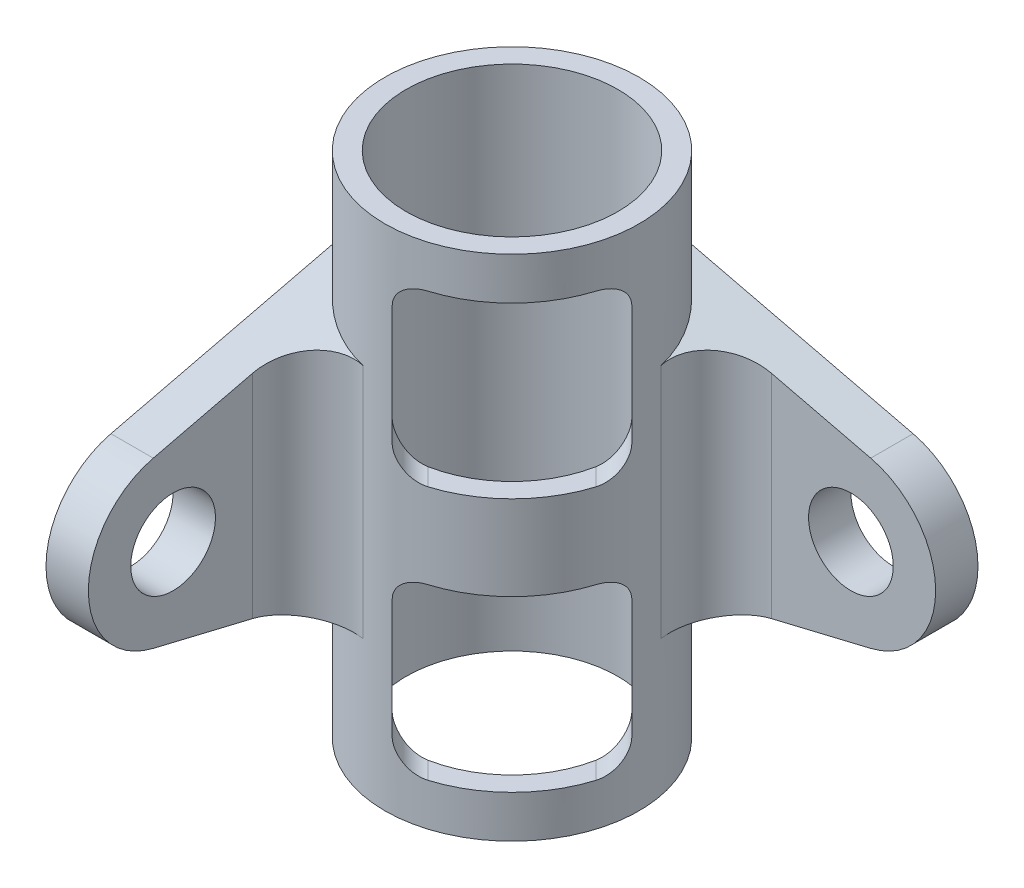
SolidWorks part; units mm, degrees
ref_plane "前基準面" through (0, 0, 0) normal (0, 0, 1) x (1, 0, 0)
ref_plane "上基準面" through (0, 0, 0) normal (0, 1, 0) x (1, 0, 0)
ref_plane "右基準面" through (0, 0, 0) normal (1, 0, 0) x (0, 0, -1)
sketch "草圖1" plane through (0, 0, 0) normal (0, 1, 0) x (1, 0, 0)
  circle A0 centre (0, 0) radius 12.5
  circle A1 centre (0, 0) radius 15
  dimension "D1" = 25
  dimension "D2" = 30
extrude "填料-伸長3" add sketch "草圖1" along normal mid plane 60 contours A1
ref_plane "平面2" through (-15, 0, 0) normal (-1, 0, 0) x (0, 0, 1)
ref_plane "平面3" through (0, 0, -15) normal (0, 0, -1) x (-1, 0, 0)
sketch "草圖4" plane through (-15, 0, 0) normal (-1, 0, 0) x (0, 0, 1)
  line L0 (0, -17.5) -> (0, 17.5)
  line L1 (32.3383, -9.7228) -> (0, -17.5)
  line L2 (32.3383, 9.7228) -> (0, 17.5)
  circle A0 centre (30, 0) radius 5
  arc A1 (32.3383, -9.7228) -> (32.3383, 9.7228) centre (30, 0) ccw
  point P4 (0, 0)
  dimension "D2" = 30
  dimension "D3" = 10
  dimension "D4" = 10
  dimension "D1" = 35
extrude "填料-伸長4" add sketch "草圖4" against normal blind 5
sketch "草圖5" plane through (0, 0, -15) normal (0, 0, -1) x (-1, 0, 0)
  line L0 (0, -17.5) -> (0, 17.5)
  line L1 (-32.3383, -9.7228) -> (0, -17.5)
  line L2 (-32.3383, 9.7228) -> (0, 17.5)
  circle A0 centre (-30, 0) radius 5
  arc A1 (-32.3383, -9.7228) -> (-32.3383, 9.7228) centre (-30, 0) cw
  point P4 (0, 0)
  point P9 (0, 0)
  point P10 (0, 0)
  dimension "D2" = 30
  dimension "D3" = 10
  dimension "D4" = 10
  dimension "D1" = 35
extrude "填料-伸長5" add sketch "草圖5" against normal blind 5
fillet "圓角1" radius 6 2 edges at (11.1803, 0, -10) (-10, 0, 11.1803)
ref_axis "基準軸1" through (0, 33, 0) along (0, -1, 0)
ref_plane "平面4" through (0, 0, 0) normal (-0.7071, 0, 0.7071) x (0, -1, 0)
sketch "草圖6" plane through (0, 0, 0) normal (-0.7071, 0, 0.7071) x (0, -1, 0)
  line L0 (30, 15) -> (-30, 15) construction
  line L1 (30, 15) -> (-30, 15)
ref_plane "平面5" through (10.6066, 0, 10.6066) normal (0.7071, 0, 0.7071) x (0.7071, 0, -0.7071)
extrude "除料-伸長4" cut sketch "草圖1<3>" against normal through all both and the other way through all contours A0
sketch "草圖1<3>" plane through (0, 0, 0) normal (0, 1, 0) x (1, 0, 0) same geometry as "草圖1"
sketch "草圖7" plane through (10.6066, 0, 10.6066) normal (0.7071, 0, 0.7071) x (0.7071, 0, -0.7071)
  line L0 (-15.6821, 0) -> (15.9807, 0) construction
  line L1 (0, -30) -> (0, 30) construction
  line L2 (-7, 25) -> (7, 25)
  line L3 (-10, 22) -> (-10, 8)
  line L4 (-7, 5) -> (7, 5)
  line L5 (10, 22) -> (10, 8)
  line L6 (-10, 25) -> (10, 5) construction
  line L7 (-10, 5) -> (10, 25) construction
  line L9 (15, 30) -> (-15, 30) construction
  line L10 (-7, -5) -> (7, -5)
  line L11 (10, -22) -> (10, -8)
  line L12 (-7, -25) -> (7, -25)
  line L13 (-10, -22) -> (-10, -8)
  arc A0 (-10, 22) -> (-7, 25) centre (-7, 22) cw
  arc A1 (10, 22) -> (7, 25) centre (7, 22) ccw
  arc A2 (-7, 5) -> (-10, 8) centre (-7, 8) cw
  arc A3 (7, 5) -> (10, 8) centre (7, 8) ccw
  arc A4 (10, -8) -> (7, -5) centre (7, -8) ccw
  arc A5 (-10, -8) -> (-7, -5) centre (-7, -8) cw
  arc A6 (-7, -25) -> (-10, -22) centre (-7, -22) cw
  arc A7 (10, -22) -> (7, -25) centre (7, -22) cw
  point P3 (0, 15)
  point P30 (10, -5)
  point P33 (-10, -5)
  point P36 (-10, -25)
  point P39 (10, -25)
  dimension "D4" = 3
  dimension "D5" = 3
  dimension "D6" = 3
  dimension "D7" = 3
  dimension "D8" = 3
  dimension "D9" = 3
  dimension "D10" = 3
  dimension "D11" = 3
  dimension "D1" = 20
  dimension "D2" = 20
  dimension "D3" = 5
extrude "除料-伸長3" cut sketch "草圖7" against normal up to surface (7.5 mm away) up to face at (0, -30, 12.5)
